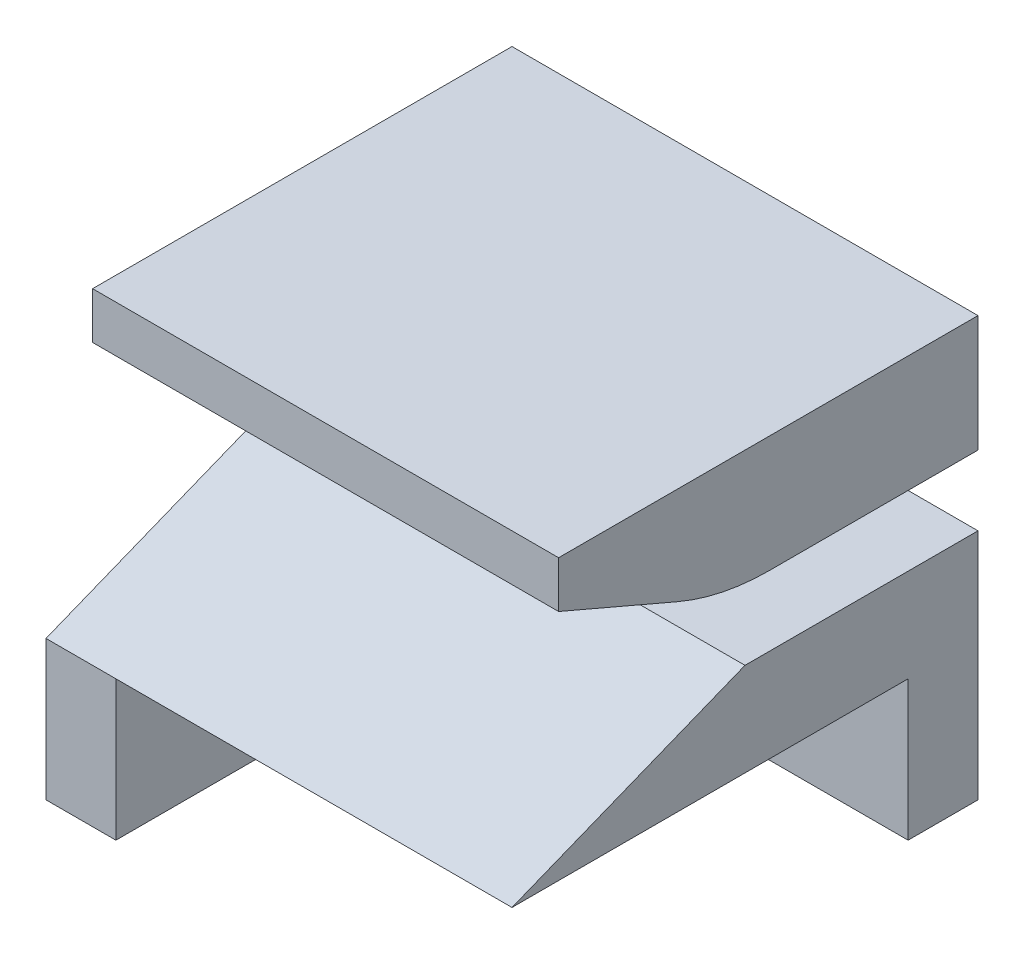
SolidWorks part; units mm, degrees
ref_plane "前视基准面" through (0, 0, 0) normal (0, 0, 1) x (1, 0, 0)
ref_plane "上视基准面" through (0, 0, 0) normal (0, 1, 0) x (1, 0, 0)
ref_plane "右视基准面" through (0, 0, 0) normal (1, 0, 0) x (0, 0, -1)
sketch "Sketch1" plane through (0, 0, 0) normal (0, 1, 0) x (1, 0, 0)
  line L1 (-10, 10) -> (10, 10)
  line L2 (-10, 10) -> (-10, -10)
  line L3 (-10, -10) -> (10, -10)
  line L4 (10, 10) -> (10, -10)
  line L5 (-10, 10) -> (10, -10) construction
  line L6 (-10, -10) -> (10, 10) construction
  point P0 (0, 0)
  dimension "D1" = 20
  dimension "D2" = 20
extrude "Boss-Extrude1" add sketch "Sketch1" along normal blind 20
sketch "Sketch2" plane through (0, 0, 0) normal (0, -1, 0) x (1, 0, 0)
  line L1 (10, 10) -> (-7, 10)
  line L2 (10, 10) -> (10, -7)
  line L3 (10, -7) -> (-7, -7)
  line L4 (-7, 10) -> (-7, -7)
  dimension "D1" = 17
  dimension "D2" = 17
extrude "Cut-Extrude1" cut sketch "Sketch2" against normal blind 16 contours L4 L3 L2 L1
sketch "Sketch3" plane through (0, 20, 0) normal (0, 1, 0) x (1, 0, 0)
  line L1 (10, 7) -> (-10, 7)
  line L2 (10, 7) -> (10, 10)
  line L3 (10, 10) -> (-10, 10)
  line L4 (-10, 7) -> (-10, 10)
extrude "Boss-Extrude3" add sketch "Sketch3" along normal blind 8
sketch "Sketch5" plane through (0, 0, -7) normal (0, 0, 1) x (1, 0, 0)
  line L0 (-10, 28) -> (-10, 20) construction
  line L1 (10, 28) -> (-10, 28)
  line L2 (10, 28) -> (10, 23)
  line L3 (10, 23) -> (-10, 23)
  line L4 (-10, 28) -> (-10, 23)
  dimension "D1" = 5
extrude "Boss-Extrude4" add sketch "Sketch5" along normal blind 15
sketch "Sketch6" plane through (-10, 0, 0) normal (-1, 0, 0) x (0, 0, 1)
  line L0 (10, 16) -> (0, 20)
  line L1 (-7, 20) -> (10, 20) construction
  line L2 (0, 20) -> (10, 20)
  line L3 (10, 20) -> (10, 16)
  line L4 (8, 26) -> (1, 23)
  line L5 (8, 28) -> (8, 23) construction
  line L6 (8, 23) -> (-7, 23) construction
  line L7 (1, 23) -> (8, 23)
  line L8 (8, 23) -> (8, 26)
  dimension "D1" = 10
  dimension "D2" = 3
  dimension "D3" = 7
extrude "Cut-Extrude2" cut sketch "Sketch6" against normal through all both and the other way through all
sketch "Sketch7" plane through (0, 0, -7) normal (0, 0, 1) x (1, 0, 0)
  line L0 (-10, 20) -> (10, 20) construction
  line L1 (10, 23) -> (4, 23)
  line L2 (10, 23) -> (10, 20)
  line L3 (10, 20) -> (4, 20)
  line L4 (4, 23) -> (4, 20)
  dimension "D1" = 6
extrude "Cut-Extrude3" cut sketch "Sketch7" against normal through all both and the other way through all
chamfer "Chamfer1" distance 3 angle 45 1 edges at (4, 21.5, -7)
sketch "Sketch8" plane through (0, 0, -7) normal (0, 0, 1) x (1, 0, 0)
  line L0 (-7, 16) -> (-7, 0) construction
  line L1 (10, 16) -> (-7, 16) construction
  circle A0 centre (0, 13) radius 1.6
  dimension "D1" = 3.2
  dimension "D2" = 7
  dimension "D3" = 3
extrude "Cut-Extrude4" cut sketch "Sketch8" against normal blind 10
sketch "Sketch9" plane through (-7, 0, 0) normal (1, 0, 0) x (0, 0, -1)
  line L0 (-10, 16) -> (7, 16) construction
  line L1 (7, 16) -> (7, 0) construction
  circle A0 centre (0, 13) radius 1.6
  dimension "D1" = 3.2
  dimension "D2" = 3
  dimension "D3" = 7
extrude "Cut-Extrude5" cut sketch "Sketch9" against normal blind 10
sketch "Sketch10" plane through (-10, 0, 0) normal (-1, 0, 0) x (0, 0, 1)
  line L0 (-10, 28) -> (-10, 0) construction
  line L1 (10, 0) -> (-10, 0)
  line L2 (10, 0) -> (10, 10)
  line L3 (10, 10) -> (-10, 10)
  line L4 (-10, 0) -> (-10, 10)
  dimension "D1" = 10
extrude "Cut-Extrude6" cut sketch "Sketch10" against normal through all both and the other way through all
sketch "Sketch11" plane through (-10, 0, 0) normal (-1, 0, 0) x (0, 0, 1)
  line L1 (-7, 23) -> (0, 23)
  line L2 (-7, 23) -> (-7, 20)
  line L3 (-7, 20) -> (0, 20)
  line L4 (0, 23) -> (0, 20)
extrude "Boss-Extrude5" add sketch "Sketch11" against normal blind 2
fillet "Fillet2" radius 1 1 edges at (-8, 21.5, -7)
chamfer "Chamfer2" distance 2 angle 45 1 edges at (-8, 21.5, 0)
fillet "Fillet3" radius 10 1 edges
